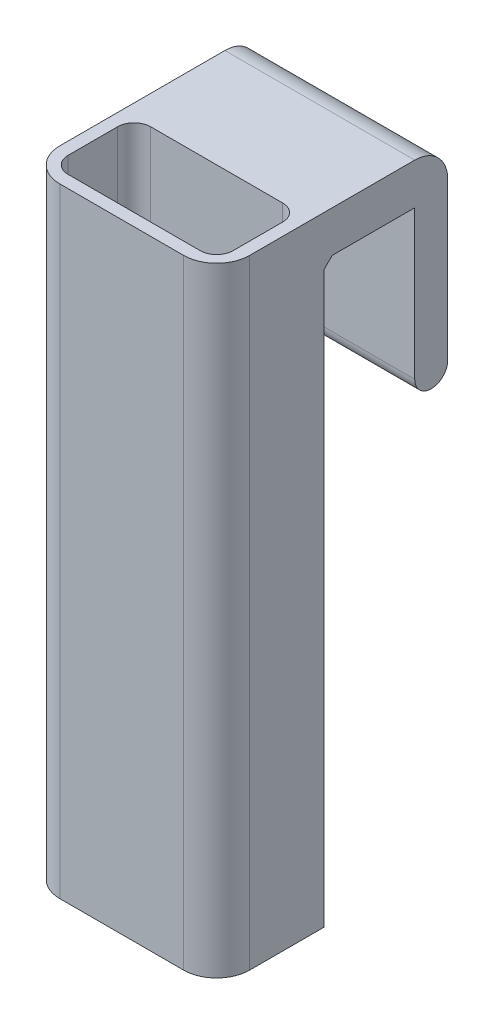
SolidWorks part; units mm, degrees
ref_plane "Front Plane" through (0, 0, 0) normal (0, 0, 1) x (1, 0, 0)
ref_plane "Top Plane" through (0, 0, 0) normal (0, 1, 0) x (1, 0, 0)
ref_plane "Right Plane" through (0, 0, 0) normal (1, 0, 0) x (0, 0, -1)
sketch "Sketch2" plane through (0, 0, 0) normal (1, 0, 0) x (0, 0, -1)
  line L1 (0, 0) -> (13, 0)
  line L2 (0, 0) -> (0, 75)
  line L3 (0, 75) -> (28, 75)
  line L4 (13, 0) -> (13, 70)
  line L5 (28, 75) -> (28, 50)
  line L6 (28, 50) -> (24, 50)
  line L7 (24, 50) -> (24, 70)
  line L8 (24, 70) -> (13, 70)
  dimension "D1" = 13
  dimension "D2" = 75
  dimension "D3" = 5
  dimension "D4" = 4
  dimension "D5" = 20
  dimension "D6" = 11
extrude "Boss-Extrude1" add sketch "Sketch2" along normal blind 23
sketch "Sketch3" plane through (0, 75, 0) normal (0, 1, 0) x (1, 0, 0)
  line L23 (23, 11.5) -> (0, 11.5)
  line L24 (21.5, 1.5) -> (21.5, 28)
  line L25 (1.5, 1.5) -> (21.5, 1.5)
  line L26 (1.5, 28) -> (1.5, 1.5)
  line L27 (21.5, 1.5) -> (21.5, 11.5)
  line L28 (1.5, 1.5) -> (21.5, 1.5)
  line L29 (1.5, 11.5) -> (1.5, 1.5)
  line L30 (21.5, 11.5) -> (1.5, 11.5)
  dimension "D1" = 1.5
  dimension "D2" = 1.5
extrude "Cut-Extrude1" cut sketch "Sketch3" against normal offset from surface (73 mm away) 2 up to face at (11.5, 0, -6.5)
chamfer "Chamfer1" distance 1 angle 45 1 edges at (11.5, 70, -13)
fillet "Fillet1" radius 4 2 edges at (0, 37.5, 0) (23, 37.5, 0)
fillet "Fillet2" radius 2 4 edges at (21.5, 38.5, -1.5) (21.5, 38.5, -11.5) (1.5, 38.5, -1.5) (1.5, 38.5, -11.5)
fillet "Fillet3" radius 4 1 edges at (11.5, 75, -28)
fillet "Fillet4" radius 2 2 edges at (11.5, 50, -28) (11.5, 50, -24)
